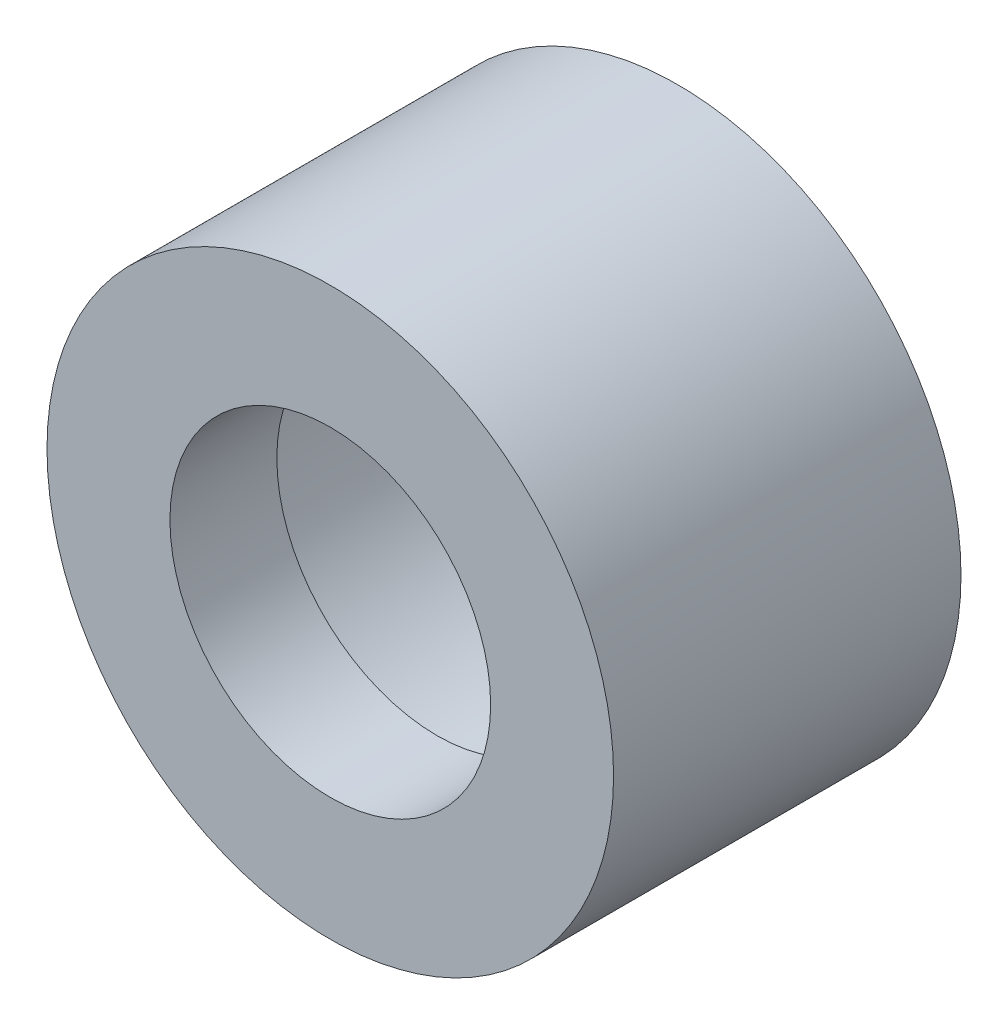
SolidWorks part; units mm, degrees
ref_plane "Front Plane" through (0, 0, 0) normal (0, 0, 1) x (1, 0, 0)
ref_plane "Top Plane" through (0, 0, 0) normal (0, 1, 0) x (1, 0, 0)
ref_plane "Right Plane" through (0, 0, 0) normal (1, 0, 0) x (0, 0, -1)
sketch "Sketch1" plane through (0, 0, 0) normal (0, 0, 1) x (1, 0, 0)
  circle A0 centre (0, 0) radius 13.462
  circle A1 centre (0, 0) radius 7.62
  circle A2 centre (0, 0) radius 10.414
  dimension "D1" = 26.924
  dimension "D2" = 15.24
  dimension "D3" = 20.828
extrude "Boss-Extrude3" add sketch "Sketch1" along normal blind 16.51 contours A0
extrude "Cut-Extrude3" cut sketch "Sketch1<15>" along normal blind 16.51 contours A1 region at (0, 0, 0)
sketch "Sketch1<15>" plane through (0, 0, 0) normal (0, 0, 1) x (1, 0, 0) same geometry as "Sketch1"
extrude "Cut-Extrude4" cut sketch "Sketch1<16>" along normal blind 11.43 contours A2 A1 region at (-10.1194, 0, 0)
sketch "Sketch1<16>" plane through (0, 0, 0) normal (0, 0, 1) x (1, 0, 0) same geometry as "Sketch1"
